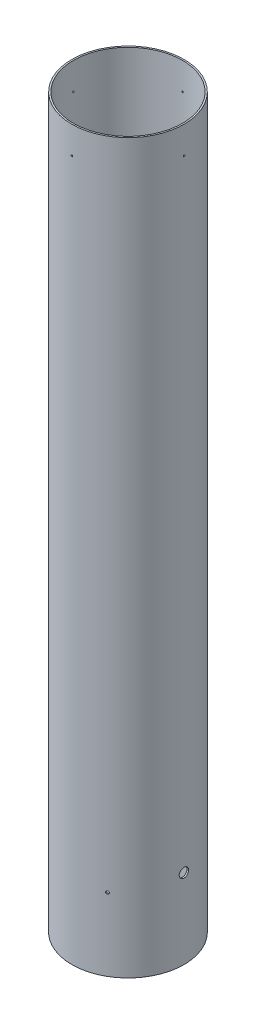
SolidWorks part; units mm, degrees
material "A-Glass Fiber"
ref_plane "Front Plane" through (0, 0, 0) normal (0, 0, 1) x (1, 0, 0)
ref_plane "Top Plane" through (0, 0, 0) normal (0, 1, 0) x (1, 0, 0)
ref_plane "Right Plane" through (0, 0, 0) normal (1, 0, 0) x (0, 0, -1)
sketch "Sketch1" plane through (0, 0, 0) normal (0, 1, 0) x (1, 0, 0)
  circle A0 centre (0, 0) radius 76.1746
  circle A1 centre (0, 0) radius 78.359
  dimension "D1" = 156.718
  dimension "D2" = 152.3492
extrude "Boss-Extrude1" add sketch "Sketch1" along normal blind 1016
ref_axis "Axis1" through (0, 1016, 0) along (0, -1, 0)
sketch "Sketch2" plane through (0, 0, 0) normal (1, 0, 0) x (0, 0, -1)
  line L0 (78.359, 1016) -> (-78.359, 1016) construction
  circle A0 centre (0, 977.9) radius 1.0922
  dimension "D1" = 2.1844
  dimension "D2" = 38.1
extrude "Cut-Extrude1" cut sketch "Sketch2" against normal through all
pattern_circular "CirPattern1" count 4 over 360 about axis through (0, 1016, 0) along (0, 1, 0) of "Cut-Extrude1"
hole_wizard "1/2 Clearance Hole1" positions "Sketch3" profile "Sketch4" hole size "1/2" standard "ANSI Inch"
sketch "Sketch3" plane through (0, 0, 0) normal (1, 0, 0) x (0, 0, -1)
  point P0 (0, 111.125)
  dimension "D1" = 111.125
sketch "Sketch4" plane through (0, 111.125, 0) normal (0, 1, 0) x (0, 0, 1)
  line L0 (0, 0) -> (0, 92.8345)
  line L1 (0, 92.8345) -> (6.5481, 88.9)
  line L2 (6.5481, 88.9) -> (6.5481, 0)
  line L5 (6.5481, 0) -> (0, 0)
  line L10 (0, 92.8345) -> (-6.5481, 88.9) construction
  line L11 (0, -6.35) -> (0, 107.95) construction
  dimension "Hole Dia." = 13.0962
  dimension "Hole Depth" = 88.9
  dimension "Drill Angle" = 118
hole_wizard "Ø4.0 (4) Diameter Hole1" positions "Sketch5" profile "Sketch6" hole size "Ø4.0" standard "ANSI Metric"
sketch "Sketch5" plane through (0, 0, 0) normal (1, 0, 0) x (0, 0, -1)
  point P0 (0, 101.6)
  dimension "D1" = 101.6
sketch "Sketch6" plane through (0, 101.6, 0) normal (0, 1, 0) x (0, 0, -1)
  line L0 (0, 0) -> (0, 90.1017)
  line L1 (0, 90.1017) -> (2, 88.9)
  line L2 (2, 88.9) -> (2, 0)
  line L5 (2, 0) -> (0, 0)
  line L10 (0, 90.1017) -> (-2, 88.9) construction
  line L11 (0, -6.35) -> (0, 107.95) construction
  dimension "Hole Dia." = 4
  dimension "Hole Depth" = 88.9
  dimension "Drill Angle" = 118
pattern_circular "CirPattern2" count 3 over 360 about axis through (0, 0, 0) along (0, 1, 0) of "Ø4.0 (4) Diameter Hole1"
equation "\"Fwd_Tube_Length\" = 40in"
equation "\"D1@Boss-Extrude1\" = \"Fwd_Tube_Length\""
equation "\"BKHD_Screw_Diam\"= 3.5mm"
equation "\"Fwd_BKHD_From_Top\" = 18in"
equation "\"Bodytube_OD\" = 6.17in"
equation "\"Bodytube_ID\" = 5.998in"
equation "\"D2@Sketch1\"=\"Bodytube_ID\""
equation "\"D1@Sketch1\"=\"Bodytube_OD\""
equation "\"Shear_Screw_Diameter\" = 0.086in"
equation "\"Shear_Screw_Coupler_Location\" = 4.5in"
equation "\"Motor_OD\" = 4in"
equation "\"Mid_Tube_Length\"= 1in"
equation "\"Mid_Coupler_Length\" = 13in"
equation "\"Aft_Section_Length\"= 36in"
equation "\"AB_Coupler_OD_Length\"= 1in"
equation "\"AB_Coupling_Section_Length\"= 0.375in"
equation "\"AB_Coupler_Length\"= \"AB_Coupler_OD_Length\" + \"AB_Coupling_Section_Length\" * 2"
equation "\"Cutout_Angle\" = 80"
equation "\"AB_Paddle_Height\" = 0.375in"
equation "\"AB_Coupler_Num_Screws\"= 4"
equation "\"AB_BKHD_Thickness\" = 0.375in"
equation "\"AB_Mount_From_Bottom\" = 23.175in"
equation "\"Num_Cutouts\" = 3"
equation "\"AB_Coupler_OD\"= 6.17in"
equation "\"AB_Coupler_ID\"= 5.75in"
equation "\"AB_Coupler_Surface_Diameter\"= 5.998in"
equation "\"AB_Coupling_Screw_Diameter\"= 0.15748in"
equation "\"AB_Central_Bushing_Length\" = .4724in"
equation "\"Lead_Screw_Dist\" = 3.4in"
equation "\"Lead_Screw_Diam\" = 0.386in"
equation "\"Lead_Screw_Length\" = (\"Mid_Coupler_Length\" + 2*0.375in + 2*.75in)"
equation "\"Paddle_Pin_Offset\" = .25in"
equation "\"Paddle_Pin_Radius\" = 2.25in"
equation "\"SS_Paddle_Pin_Radius\" = 2.25*0.66in"
equation "\"Paddle_Gear_OD\" = 3.2in"
equation "\"Drive_Gear_OD\" = 1.7in"
equation "\"Fin_Thickness\"= .118in"
equation "\"Guiderail_Cutout_Diameter\"= 1.5in"
equation "\"DB9_Hole_Dist\" = 25mm"
equation "\"DB9_Relief_Width\" = 0.47in"
equation "\"DB9_Relief_Hole_Offset\" = 0.09in"
equation "\"Airbrakes_Wire_Hole_Dia\" = .25in"
equation "\"Airbrakes_Wire_Hole_Dist\" = 1.1in"
equation "\"Servo_Gear_Offset\" = 0.5in"
equation "\"D1@Sketch2\"=\"Shear_Screw_Diameter\""
equation "\"FWD_Shear_Screw_Dist\" = 1.5in"
equation "\"D2@Sketch2\"=\"FWD_Shear_Screw_Dist\""
